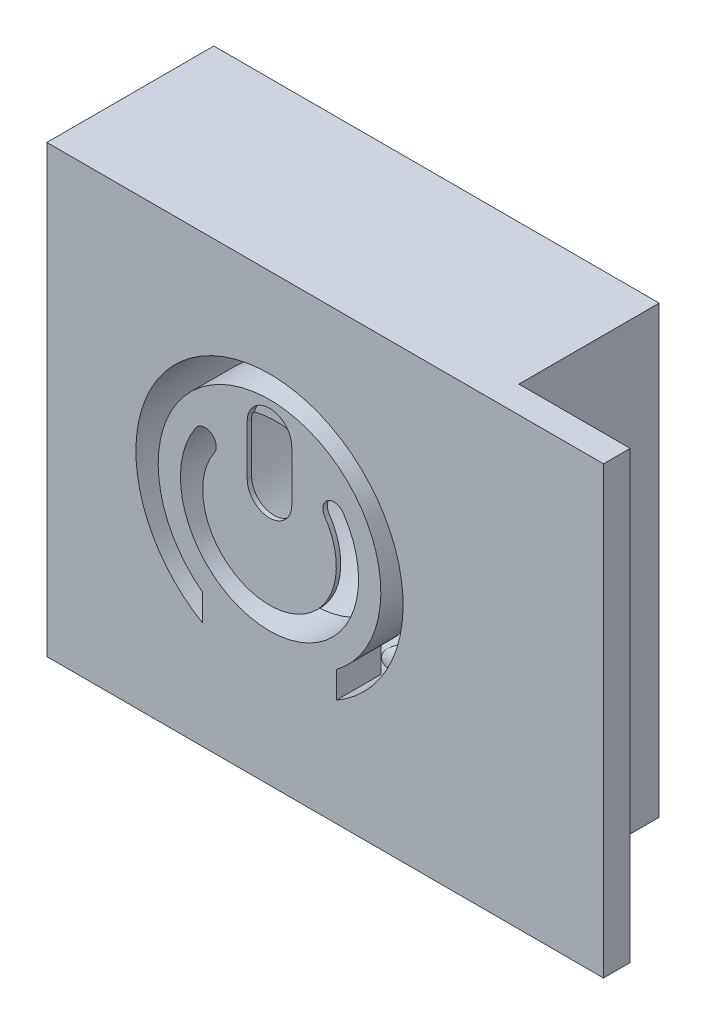
SolidWorks part; units mm, degrees
material "ABS"
ref_plane "Front Plane" through (0, 0, 0) normal (0, 0, 1) x (1, 0, 0)
ref_plane "Top Plane" through (0, 0, 0) normal (0, 1, 0) x (1, 0, 0)
ref_plane "Right Plane" through (0, 0, 0) normal (1, 0, 0) x (0, 0, -1)
sketch "Sketch1" plane through (0, 0, 0) normal (0, 0, 1) x (1, 0, 0)
  line L1 (-10, 10) -> (10, 10)
  line L2 (-10, 10) -> (-10, -10)
  line L3 (-10, -10) -> (10, -10)
  line L4 (10, 10) -> (10, -10)
  line L5 (-10, 10) -> (10, -10) construction
  line L6 (-10, -10) -> (10, 10) construction
  point P0 (0, 0)
  dimension "D1" = 20
  dimension "D2" = 20
extrude "Boss-Extrude1" add sketch "Sketch1" along normal blind 7.5
sketch "Sketch2" plane through (0, 0, 0) normal (0, 0, -1) x (-1, 0, 0)
  circle A0 centre (0, 0) radius 6
  dimension "D1" = 12
extrude "Cut-Extrude1" cut sketch "Sketch2" against normal blind 5.5
sketch "Sketch3" plane through (0, 0, 5.5) normal (0, 0, -1) x (-1, 0, 0)
  line L0 (-3, -4) -> (-3, -5.1962)
  line L1 (0, 6) -> (0, -6) construction
  line L2 (3, -4) -> (3, -5.1962)
  arc A0 (3, -5.1962) -> (-3, -5.1962) centre (0, 0) ccw
  circle A1 centre (0, 0) radius 5
  circle A2 centre (0, 0) radius 6 construction
  circle M5 centre (0, 0) radius 6
  dimension "D1" = 10
  dimension "D2" = 3
extrude "Cut-Extrude2" cut sketch "Sketch3" against normal blind 5 contours L1 A0 L0 A1 | L1 A1 L2 M5 region at (3.127, -4.5981, 5.5) region at (-0.127, 5.5, 5.5)
sketch "Sketch4" plane through (0, 0, 5.5) normal (0, 0, -1) x (-1, 0, 0)
  circle A0 centre (0, 0) radius 4
  dimension "D1" = 8
extrude "Cut-Extrude3" cut sketch "Sketch4" against normal blind 1.8
sketch "Sketch5" plane through (0, 0, 7.5) normal (0, 0, 1) x (1, 0, 0)
  line L0 (0, 3.6628) -> (0, 1.394) construction
  line L1 (-1, 3.6628) -> (-1, 1.394)
  line L2 (1, 3.6628) -> (1, 1.394)
  arc A0 (-1, 3.6628) -> (1, 3.6628) centre (0, 3.6628) cw
  arc A1 (-1, 1.394) -> (1, 1.394) centre (0, 1.394) ccw
  arc A2 (-2.4828, 1.684) -> (2.4828, 1.684) centre (0, 0) ccw
  arc A3 (-3.3104, 2.2453) -> (3.3104, 2.2453) centre (0, 0) ccw
  arc A4 (-2.4828, 1.684) -> (-3.3104, 2.2453) centre (-2.8966, 1.9647) ccw
  arc A5 (2.4828, 1.684) -> (3.3104, 2.2453) centre (2.8966, 1.9647) cw
  dimension "D4" = 3
  dimension "D1" = 1
  dimension "D2" = 1
  dimension "D3" = 1
extrude "Cut-Extrude4" cut sketch "Sketch5" against normal blind 0.3
sketch "Sketch6" plane through (0, 0, 0) normal (0, 0, -1) x (-1, 0, 0)
  line L0 (0, 10) -> (0, -10) construction
  line L1 (6.5, 2.75) -> (8.5, 2.75)
  line L2 (6.5, 2.75) -> (6.5, -2.75)
  line L3 (6.5, -2.75) -> (8.5, -2.75)
  line L4 (8.5, 2.75) -> (8.5, -2.75)
  line L5 (6.5, 2.75) -> (8.5, -2.75) construction
  line L6 (6.5, -2.75) -> (8.5, 2.75) construction
  line L7 (-2.75, -6.5) -> (2.75, -6.5)
  line L8 (-2.75, -6.5) -> (-2.75, -8.5)
  line L9 (-2.75, -8.5) -> (2.75, -8.5)
  line L10 (2.75, -6.5) -> (2.75, -8.5)
  line L11 (-2.75, -6.5) -> (2.75, -8.5) construction
  line L12 (-2.75, -8.5) -> (2.75, -6.5) construction
  line L13 (-10, 10) -> (10, 10) construction
  line L14 (10, -10) -> (-10, -10) construction
  line L15 (-10, 0) -> (10, 0) construction
  line L16 (-10, -10) -> (-10, 10) construction
  line L17 (10, 10) -> (10, -10) construction
  point P0 (7.5, 0)
  point P5 (0, -7.5)
  dimension "D1" = 2
  dimension "D2" = 5.5
  dimension "D3" = 1.5
  dimension "D4" = 1.5
extrude "Cut-Extrude5" cut sketch "Sketch6" against normal blind 7
sketch "Sketch7" plane through (-10, 0, 0) normal (-1, 0, 0) x (0, 0, 1)
  line L0 (0, 0) -> (7.5, 0) construction
  line L1 (7.5, 10) -> (7.5, -10) construction
  circle A0 centre (3.75, 0) radius 1.5
  dimension "D1" = 3
extrude "Cut-Extrude6" cut sketch "Sketch7" against normal up to next
sketch "Sketch8" plane through (0, -10, 0) normal (0, -1, 0) x (-1, 0, 0)
  line L0 (0, -7.5) -> (0, 0) construction
  line L1 (10, -7.5) -> (-10, -7.5) construction
  line L2 (10, 0) -> (-10, 0) construction
  circle A0 centre (0, -3.75) radius 1.5
  dimension "D1" = 3
extrude "Cut-Extrude7" cut sketch "Sketch8" against normal up to next
sketch "Sketch9" plane through (10, 0, 0) normal (1, 0, 0) x (0, 0, -1)
  line L0 (0, 0) -> (-7.5, 0) construction
  line L1 (-7.5, -10) -> (-7.5, 10) construction
  line L2 (-3.75, 10) -> (-3.75, 0) construction
  line L3 (-7.5, 10) -> (0, 10) construction
  circle A0 centre (-3.75, 4) radius 1.8
  circle A1 centre (-3.75, -4) radius 1.8
  point P11 (0, 0)
  dimension "D1" = 3.6
  dimension "D2" = 4
extrude "Cut-Extrude8" cut sketch "Sketch9" against normal up to next
sketch "Sketch10" plane through (10, 0, 0) normal (1, 0, 0) x (0, 0, -1)
  line L0 (-7.5, -10) -> (0, -10) construction
  line L1 (-7.5, 10) -> (-6.3, 10)
  line L2 (-7.5, 10) -> (-7.5, -10)
  line L3 (-7.5, -10) -> (-6.3, -10)
  line L4 (-6.3, 10) -> (-6.3, -10)
  dimension "D1" = 1.2
extrude "Boss-Extrude2" add sketch "Sketch10" along normal blind 5
sketch "Sketch11" plane through (0, 0, 5.5) normal (0, 0, -1) x (-1, 0, 0)
  line L0 (0, 0) -> (0, 4.5) construction
  circle A0 centre (0, 4.5) radius 0.5
  arc A1 (3, -4) -> (-3, -4) centre (0, 0) ccw construction
  circle A2 centre (0, 0) radius 4 construction
extrude "Boss-Extrude3" add sketch "Sketch11" along normal blind 2
sketch "Sketch12" plane through (0, 0, 0) normal (0, 0, -1) x (-1, 0, 0)
  line L0 (0, 0) -> (0, 4.5) construction
  line L18 (-3.33, 6.575) -> (3.33, 6.575)
  line L19 (-3.33, 6.575) -> (-3.33, 2.425)
  line L20 (-3.33, 2.425) -> (3.33, 2.425)
  line L21 (3.33, 6.575) -> (3.33, 2.425)
  line L22 (-3.33, 6.575) -> (3.33, 2.425) construction
  line L23 (-3.33, 2.425) -> (3.33, 6.575) construction
  dimension "D1" = 6.66
  dimension "D2" = 4.15
extrude "Cut-Extrude9" cut sketch "Sketch12" against normal up to surface (3.5 mm away) up to face at (-0.5, 4.5, 3.5)
sketch "Sketch13" plane through (0, 0, 0) normal (0, 0, -1) x (-1, 0, 0)
  line L0 (3.33, 6.575) -> (3.33, 4.9911) construction
  line L1 (-3.33, 6.575) -> (3.33, 6.575)
  line L2 (-3.33, 6.575) -> (-3.33, 2.425)
  line L3 (-3.33, 2.425) -> (3.33, 2.425)
  line L4 (3.33, 6.575) -> (3.33, 2.425)
  line L5 (-5.33, 0.425) -> (5.33, 0.425)
  line L6 (5.33, 8.575) -> (5.33, 0.425)
  line L7 (-5.33, 8.575) -> (5.33, 8.575)
  line L8 (-5.33, 8.575) -> (-5.33, 0.425)
  dimension "D1" = 4.15
  dimension "D2" = 2
extrude "Boss-Extrude4" add sketch "Sketch13" along direction (0, 0, -1) on the side against the normal blind 2.5
